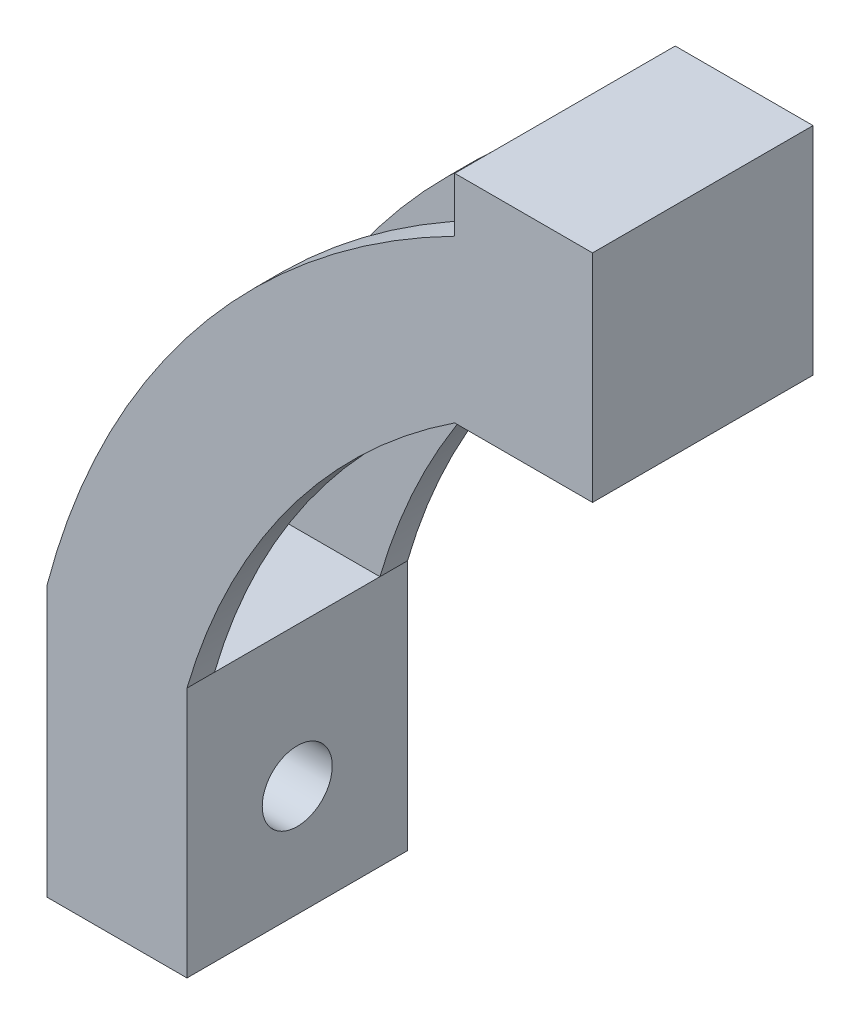
SolidWorks part; units mm, degrees
ref_plane "Front Plane" through (0, 0, 0) normal (0, 0, 1) x (1, 0, 0)
ref_plane "Top Plane" through (0, 0, 0) normal (0, 1, 0) x (1, 0, 0)
ref_plane "Right Plane" through (0, 0, 0) normal (1, 0, 0) x (0, 0, -1)
sketch "Arm Geometry" plane through (0, 0, 0) normal (0, 0, 1) x (1, 0, 0)
  line L0 (-124.4229, 7.4414) -> (124.4229, 7.4414) construction
  line L1 (0, 0) -> (0, 124.6452) construction
  line L2 (0, 124.6452) -> (-124.4229, 124.6452) construction
  line L3 (-124.4229, 7.4414) -> (-124.4229, 124.6452) construction
  circle A0 centre (0, 0) radius 124.6452 construction
ref_plane "Motor Mount interface" through (-40.08, 0, 0) normal (1, 0, 0) x (0, 0, -1)
ref_plane "Counter Weight Interface" through (0, -12.7, 0) normal (0, 1, 0) x (1, 0, 0)
ref_plane "Arm Width (z+)" through (0, 0, 20) normal (0, 0, 1) x (1, 0, 0)
ref_plane "Arm Width (z-)" through (0, 0, -20) normal (0, 0, 1) x (1, 0, 0)
ref_axis "Arm Rotational Axis" through (-124.4229, 7.4414, 0) along (1, 0, 0)
ref_plane "Counterweight Location Plane" through (-124.4229, 0, 0) normal (1, 0, 0) x (0, 0, -1)
sketch "Sketch3" plane through (0, 0, 0) normal (1, 0, 0) x (0, 0, -1)
  line L0 (-20, 138.8432) -> (-20, -138.8432) construction
  line L1 (20, 32.8414) -> (-20, 32.8414)
  line L2 (20, 32.8414) -> (20, -12.7)
  line L3 (20, -12.7) -> (-20, -12.7)
  line L4 (-20, 32.8414) -> (-20, -12.7)
  line L5 (22, -12.7) -> (-22, -12.7) construction
  line L6 (20, 138.8432) -> (20, -138.8432) construction
  dimension "D1" = 25.4
extrude "Boss-Extrude2" add sketch "Sketch3" along normal blind 300 and the other way blind 300
sketch "Sketch2" plane through (0, 0, 0) normal (0, 0, 1) x (1, 0, 0)
  line L0 (0, 0) -> (286.3082, 0) construction
  line L1 (105.5952, 0) -> (-143.6952, 0)
  line L2 (105.5952, 0) -> (143.6952, 0)
  circle A2 centre (0, 0) radius 124.6452 construction
  arc A3 (143.6952, 0) -> (-143.6952, 0) centre (0, 0) ccw
  point P4 (124.6452, 0)
  dimension "D1" = 38.1
extrude "Boss-Extrude1" add sketch "Sketch2" along normal up to surface (20 mm away) and the other way up to surface (20 mm away) up to plane "Arm Width (z+)" other way up to plane "Arm Width (z-)"
sketch "Sketch4" plane through (0, 0, 0) normal (0, 0, 1) x (1, 0, 0)
  line L0 (113.6451, 32.8414) -> (113.6451, -47.6097)
  line L1 (113.6451, -47.6097) -> (-113.6451, -47.6097)
  line L2 (-113.6451, -47.6097) -> (-113.6451, 32.8414)
  line L3 (-300, 32.8414) -> (-139.892, 32.8414) construction
  arc A0 (113.6451, 32.8414) -> (-113.6451, 32.8414) centre (0, 0) ccw
  arc A3 (139.892, 32.8414) -> (-139.892, 32.8414) centre (0, 0) ccw construction
  dimension "D1" = 25.4
extrude "Cut-Extrude1" cut sketch "Sketch4" against normal through all both and the other way through all
sketch "Sketch6" plane through (-163.2302, 0, 0) normal (-1, 0, 0) x (0, 0, 1)
  circle A0 centre (0, 7.4414) radius 6.35
  dimension "D1" = 12.7
extrude "Cut-Extrude3" cut sketch "Sketch6" against normal through all
sketch "Sketch7" plane through (0, 0, 0) normal (1, 0, 0) x (0, 0, -1)
  line L1 (15, 32.8414) -> (-15, 32.8414)
  line L2 (15, 32.8414) -> (15, 532.8414)
  line L3 (15, 532.8414) -> (-15, 532.8414)
  line L4 (-15, 32.8414) -> (-15, 532.8414)
  point P4 (0, 32.8414)
  dimension "D1" = 500
  dimension "D2" = 30
  dimension "D3" = 25.4
extrude "Cut-Extrude4" cut sketch "Sketch7" against normal through all
sketch "Sketch9" plane through (0, 0, 0) normal (0, 0, 1) x (1, 0, 0)
  line L1 (-40.08, 612.7) -> (677.6193, 612.7)
  line L2 (-40.08, 612.7) -> (-40.08, -234.3489)
  line L3 (-40.08, -234.3489) -> (677.6193, -234.3489)
  line L4 (677.6193, 612.7) -> (677.6193, -234.3489)
  line L5 (-40.08, -22) -> (-40.08, 22) construction
  dimension "D2" = 847.0489
  dimension "D3" = 600
  dimension "D4" = 717.6993
extrude "Cut-Extrude6" cut sketch "Sketch9" along normal through all and the other way through all
sketch "Sketch11" plane through (0, 0, 0) normal (0, 0, 1) x (1, 0, 0)
  line L1 (-65.08, 137.9924) -> (-40.08, 137.9924)
  line L2 (-65.08, 137.9924) -> (-65.08, 98.7844)
  line L3 (-65.08, 98.7844) -> (-40.08, 98.7844)
  line L4 (-40.08, 137.9924) -> (-40.08, 98.7844)
  line L5 (-40.08, -22) -> (-40.08, 22) construction
  arc A0 (-40.08, 111.2985) -> (-113.6451, 32.8414) centre (0, 0) ccw construction
  dimension "D2" = 25
extrude "Boss-Extrude4" add sketch "Sketch11" along normal up to surface (20 mm away) and the other way up to surface (20 mm away) contours L2 L3 L4 L1 up to face at (-153.0011, 49.2528, 20) other way up to face at (-153.0011, 49.2528, -20)
sketch "Sketch15" plane through (0, 0, 0) normal (0, 0, 1) x (1, 0, 0)
  line L0 (-113.6451, 32.8414) -> (-113.6451, -12.7) construction
  line L1 (-439.0451, 102.7207) -> (-139.0451, 102.7207)
  line L2 (-439.0451, 102.7207) -> (-439.0451, -32.2793)
  line L3 (-439.0451, -32.2793) -> (-139.0451, -32.2793)
  line L4 (-139.0451, 102.7207) -> (-139.0451, -32.2793)
  dimension "D1" = 25.4
  dimension "D2" = 102.7207
  dimension "D3" = 300
  dimension "D4" = 135
extrude "Cut-Extrude9" cut sketch "Sketch15" against normal through all both and the other way through all
sketch "Sketch12" plane through (0, 0, 0) normal (0, 0, 1) x (1, 0, 0)
  line L0 (-40.0804, 143.6952) -> (-40.0804, 105.5952)
  line L1 (0, 124.6452) -> (-124.4229, 124.6452) construction
  line L2 (0, 0) -> (0, 124.6452) construction
  line L3 (22, -12.7) -> (-22, -12.7) construction
  line L5 (-105.3729, 7.4414) -> (-143.4729, 7.4414) construction
  line L6 (-143.4729, 7.4414) -> (-143.4729, -12.7)
  line L7 (-143.4729, 143.6952) -> (-143.4729, 7.4414)
  line L8 (0, 143.6952) -> (-143.4729, 143.6952)
  line L9 (-143.4729, 143.6952) -> (-143.4729, 7.4414)
  line L10 (-40.0804, 143.6952) -> (-143.4729, 143.6952)
  line L11 (-105.3729, 105.5952) -> (-105.3729, 7.4414)
  line L12 (0, 105.5952) -> (-105.3729, 105.5952)
  line L13 (-105.3729, 105.5952) -> (-105.3729, 7.4414)
  line L14 (-40.0804, 105.5952) -> (-105.3729, 105.5952)
  line L15 (-105.3729, 7.4414) -> (-105.3729, -12.7)
  line L16 (-143.4729, -12.7) -> (-105.3729, -12.7)
  point P2 (-40.0804, 124.6452)
  dimension "D4" = 40.0804
  dimension "D1" = 19.05
  dimension "D2" = 19.05
extrude "Boss-Extrude5" [suppressed] add sketch "Sketch12" along normal up to surface and the other way up to surface
sketch "Sketch13" plane through (0, 0, 0) normal (1, 0, 0) x (0, 0, -1)
  circle A1 centre (0, 7.4414) radius 6.35
  dimension "D1" = 12.7
extrude "Cut-Extrude7" [suppressed] cut sketch "Sketch13" against normal through all and the other way through all
sketch "Sketch14" [suppressed] plane through (0, 202.1898, 0) normal (0, 1, 0) x (1, 0, 0)
  line L1 (-46.4304, 19.05) -> (-357.6468, 19.05)
  line L2 (-46.4304, 19.05) -> (-46.4304, -19.05)
  line L3 (-46.4304, -19.05) -> (-357.6468, -19.05)
  line L4 (-357.6468, 19.05) -> (-357.6468, -19.05)
  line L7 (-46.4304, 0) -> (-357.6468, 0) construction
  line L9 (-202.0386, 25.4) -> (-202.0386, -25.4) construction
  line L10 (-40.0804, 25.4) -> (-40.0804, -25.4) construction
  point P8 (-202.0386, 0)
  dimension "D1" = 38.1
  dimension "D2" = 6.35
extrude "Cut-Extrude8" [suppressed] cut sketch "Sketch14" against normal offset from surface (164.8898 mm away) 50
